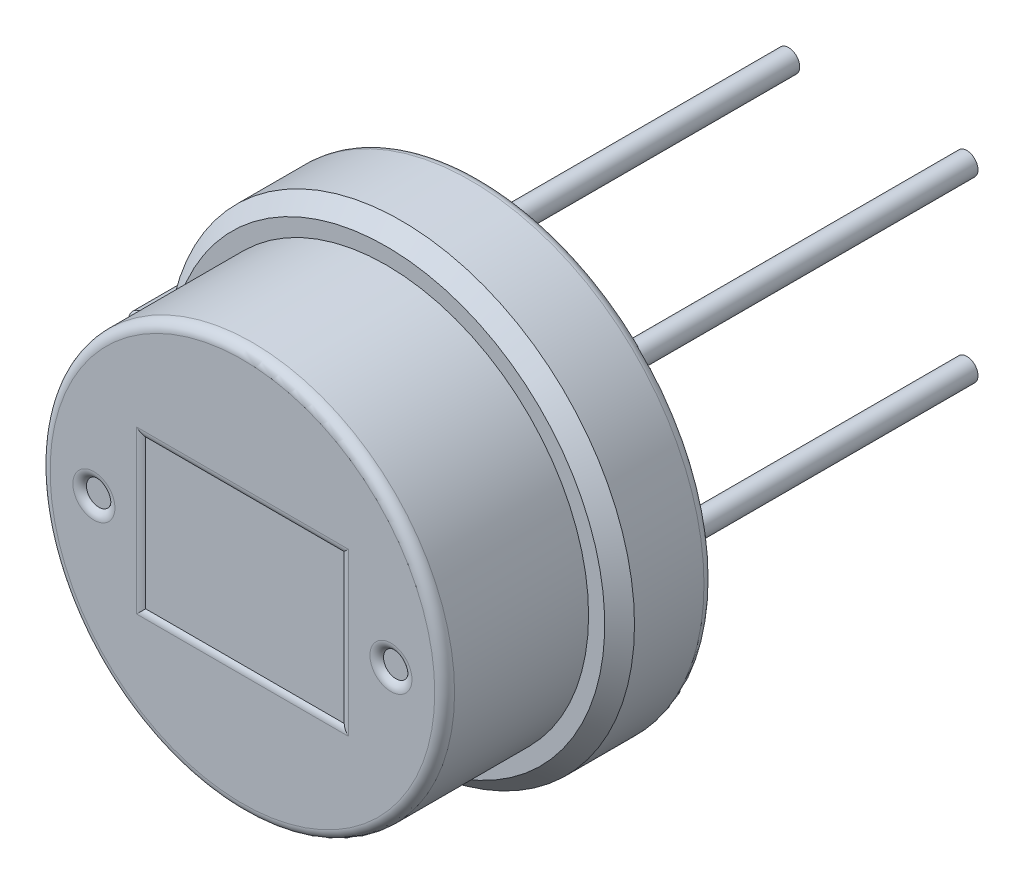
SolidWorks part; units mm, degrees
ref_plane "前视基准面" through (0, 0, 0) normal (0, 0, 1) x (1, 0, 0)
ref_plane "上视基准面" through (0, 0, 0) normal (0, 1, 0) x (1, 0, 0)
ref_plane "右视基准面" through (0, 0, 0) normal (1, 0, 0) x (0, 0, -1)
sketch "草图2" plane through (0, 0, 0) normal (0, 0, 1) x (1, 0, 0)
  line L0 (0, 6.1771) -> (0, -6.8536) construction
  line L1 (6.371, 0) -> (-6.6033, 0) construction
  line L2 (-5.5, 0.2) -> (-5.5, -0.2)
  line L3 (-5.2, -0.5) -> (-4.9356, -0.5)
  line L4 (-5.2, 0.5) -> (-4.9356, 0.5)
  arc A0 (-4.6394, -0.752) -> (-4.6394, 0.752) centre (0, 0) ccw
  arc A1 (-5.2, -0.5) -> (-5.5, -0.2) centre (-5.2, -0.2) cw
  arc A2 (-5.5, 0.2) -> (-5.2, 0.5) centre (-5.2, 0.2) cw
  arc A3 (-4.6394, -0.752) -> (-4.9356, -0.5) centre (-4.9356, -0.8) ccw
  arc A4 (-4.6394, 0.752) -> (-4.9356, 0.5) centre (-4.9356, 0.8) cw
  point P12 (-5.5, 0)
  point P14 (-5.5, -0.5)
  point P17 (-5.5, 0.5)
  point P19 (-4.6733, -0.5)
  point P22 (-4.6733, 0.5)
  dimension "D1" = 9.4
  dimension "D4" = 0.3
  dimension "D5" = 0.3
  dimension "D2" = 1
  dimension "D3" = 5.5
extrude "基座" add sketch "草图2" along normal blind 1.9
sketch "草图3" plane through (0, 0, 1.9) normal (0, 0, 1) x (1, 0, 0)
  circle A0 centre (0, 0) radius 4.075
  dimension "D1" = 8.15
extrude "封装体" add sketch "草图3" along normal blind 2.9
sketch "草图6" plane through (0, 0, 4.8) normal (0, 0, 1) x (1, 0, 0)
  line L1 (-2, 1.5) -> (2, 1.5)
  line L2 (-2, 1.5) -> (-2, -1.5)
  line L3 (-2, -1.5) -> (2, -1.5)
  line L4 (2, 1.5) -> (2, -1.5)
  line L5 (-2, 1.5) -> (2, -1.5) construction
  line L6 (-2, -1.5) -> (2, 1.5) construction
  point P0 (0, 0)
  dimension "D1" = 4
  dimension "D2" = 3
extrude "窗口" cut sketch "草图6" against normal blind 0.05
sketch "草图7" plane through (0, 0, 4.8) normal (0, 0, 1) x (1, 0, 0)
  line L0 (-6.0236, 0) -> (5.7873, 0) construction
  line L1 (0, 5.1414) -> (0, -5.3043) construction
  circle A4 centre (-2.9926, 0) radius 0.25
  circle A5 centre (2.9926, 0) radius 0.25
  dimension "D1" = 0.5
extrude "压点" cut sketch "草图7" against normal blind 0.1
sketch "草图4" plane through (0, 0, 0) normal (0, 0, -1) x (-1, 0, 0)
  line L0 (0, -4.9981) -> (0, 5.1357) construction
  line L1 (-5.2049, 0) -> (6.3427, 0) construction
  line L2 (0, 0) -> (-4.2904, -4.2904) construction
  line L3 (0, 0) -> (-1.7961, 1.7961) construction
  circle A0 centre (0, 0) radius 2.54 construction
  circle A1 centre (-1.7961, -1.7961) radius 0.225
  circle A2 centre (-1.7961, 1.7961) radius 0.225
  circle A7 centre (1.7961, -1.7961) radius 0.225
  circle A8 centre (1.7961, 1.7961) radius 0.225
  dimension "D1" = 5.08
  dimension "D3" = 0.45
  dimension "D6" = 0.45
  dimension "D2" = 45
  dimension "D4" = 45
extrude "引脚" add sketch "草图4" along normal blind 8
chamfer "倒角1" distance 0.3 angle 45 8 edges at (-5.5, 0, 1.9) (-5.4121, -0.4121, 1.9) (-5.4121, 0.4121, 1.9) (-5.0678, -0.5, 1.9) (-5.0678, 0.5, 1.9) (-4.7412, -0.5715, 1.9) (-4.7412, 0.5715, 1.9) (4.7, 0, 1.9)
fillet "圆角1" radius 0.2 15 edges at (-4.7412, -0.5715, 0) (-5.0678, -0.5, 0) (-5.4121, -0.4121, 0) (-5.5, 0, 0) (-5.4121, 0.4121, 0) (-5.0678, 0.5, 0) (-4.7412, 0.5715, 0) (4.075, 0, 4.8) (4.7, 0, 0) (2.7426, 0, 4.8) (-2.7426, 0, 4.8) (0, 1.5, 4.8) (-2, 0, 4.8) (0, -1.5, 4.8) (2, 0, 4.8)
